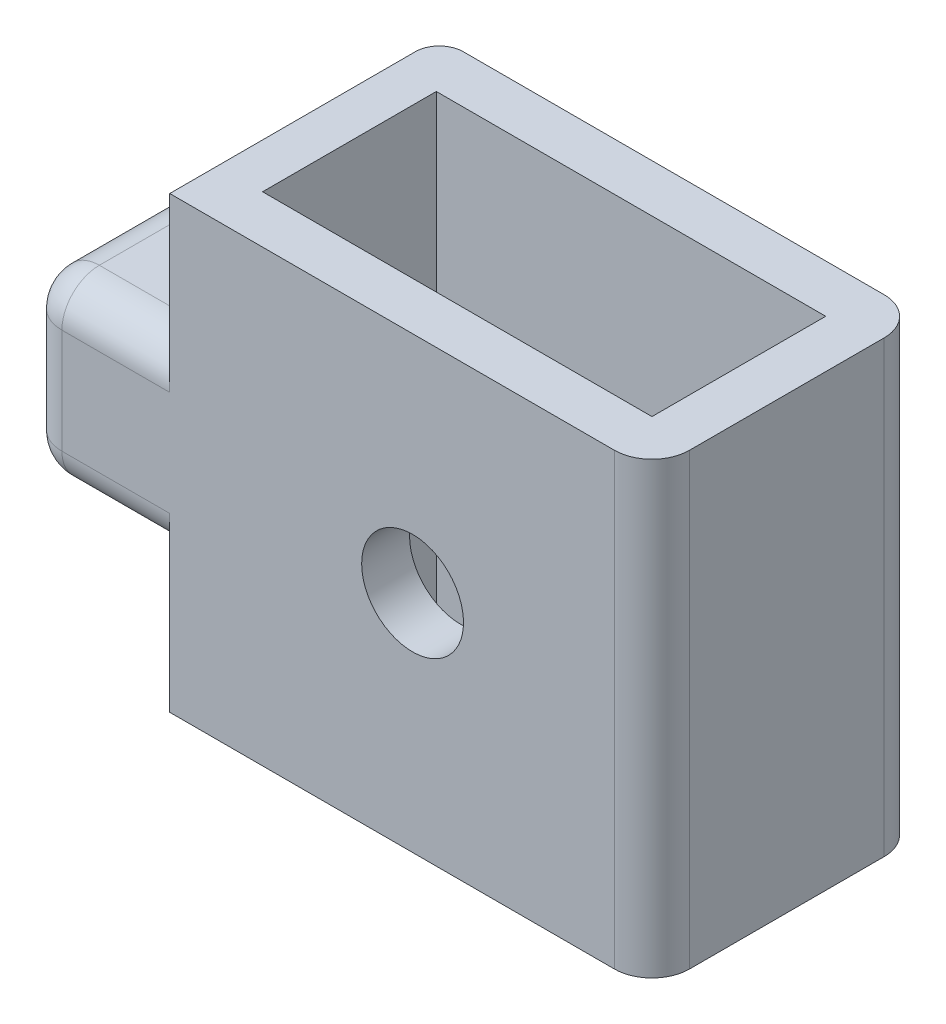
SolidWorks part; units mm, degrees
ref_plane "Спереди" through (0, 0, 0) normal (0, 0, 1) x (1, 0, 0)
ref_plane "Сверху" through (0, 0, 0) normal (0, 1, 0) x (1, 0, 0)
ref_plane "Справа" through (0, 0, 0) normal (1, 0, 0) x (0, 0, -1)
sketch "Эскиз1" plane through (0, 0, 0) normal (0, 1, 0) x (1, 0, 0)
  line L1 (25, 0) -> (394, 0)
  line L2 (0, 25) -> (0, 131.982)
  line L3 (113, 180) -> (394, 180)
  line L4 (419, 25) -> (419, 155)
  line L7 (25, 156.982) -> (91, 156.982)
  line L8 (97, 164) -> (97, 162.982)
  arc A0 (113, 180) -> (97, 164) centre (113, 164) ccw
  arc A1 (91, 156.982) -> (97, 162.982) centre (91, 162.982) ccw
  arc A2 (394, 180) -> (419, 155) centre (394, 155) cw
  arc A3 (394, 0) -> (419, 25) centre (394, 25) ccw
  arc A4 (25, 0) -> (0, 25) centre (25, 25) cw
  arc A5 (0, 131.982) -> (25, 156.982) centre (25, 131.982) cw
  point P2 (0, 0)
  point P18 (0, 0)
  dimension "D1" = 16
  dimension "D2" = 6
  dimension "D3" = 25
extrude "Бобышка-Вытянуть1" add sketch "Эскиз1" along normal blind 300
sketch "Эскиз2" plane through (0, 300, 0) normal (0, 1, 0) x (1, 0, 0)
  line L0 (394, 180) -> (113, 180) construction
  line L1 (127, 148) -> (387, 148)
  line L2 (127, 148) -> (127, 32)
  line L3 (127, 32) -> (387, 32)
  line L4 (387, 148) -> (387, 32)
  line L5 (419, 25) -> (419, 155) construction
  line L6 (25, 0) -> (394, 0) construction
  line L7 (0, 131.982) -> (0, 25) construction
  point P10 (0, 0)
  point P11 (0, 0)
  dimension "D1" = 260
  dimension "D2" = 116
  dimension "D3" = 32
  dimension "D4" = 32
  dimension "D5" = 32
  dimension "D6" = 127
extrude "Вырез-Вытянуть1" cut sketch "Эскиз2" against normal blind 300
sketch "Эскиз3" plane through (0, 300, 0) normal (0, 1, 0) x (1, 0, 0)
  line L0 (127, 148) -> (127, 32) construction
  line L1 (32, 124.982) -> (97, 124.982)
  line L2 (32, 124.982) -> (32, 32)
  line L3 (32, 32) -> (97, 32)
  line L4 (97, 124.982) -> (97, 32)
  line L5 (0, 131.982) -> (0, 25) construction
  line L6 (91, 156.982) -> (25, 156.982) construction
  line L7 (25, 0) -> (394, 0) construction
  point P8 (0, 0)
  dimension "D1" = 65
  dimension "D2" = 92.982
  dimension "D3" = 30
  dimension "D4" = 32
  dimension "D5" = 32
  dimension "D6" = 32
extrude "Вырез-Вытянуть2" cut sketch "Эскиз3" against normal blind 300
sketch "Эскиз5" plane through (0, 0, 0) normal (-1, 0, 0) x (0, 0, 1)
  line L0 (-131.982, 300) -> (-25, 300) construction
  line L1 (-131.982, 0) -> (-25, 0) construction
  line L3 (0, 300) -> (0, 0) construction
  line L4 (-156.982, 300) -> (-156.982, 0) construction
  circle A0 centre (-74.982, 150) radius 29
  dimension "D1" = 58
  dimension "D2" = 150
  dimension "D3" = 150
  dimension "D4" = 74.982
  dimension "D5" = 82
extrude "Вырез-Вытянуть4" cut sketch "Эскиз5" against normal blind 116 contours A0
sketch "Эскиз6" plane through (116, 0, 0) normal (-1, 0, 0) x (0, 0, 1)
  line L0 (-32, 300) -> (-124.982, 300) construction
  line L1 (-156.982, 300) -> (-156.982, 0) construction
  circle A0 centre (-74.982, 150) radius 23
  dimension "D1" = 46
  dimension "D2" = 150
  dimension "D3" = 82
extrude "Вырез-Вытянуть5" cut sketch "Эскиз6" against normal blind 116
sketch "Эскиз7" plane through (0, 0, -180) normal (0, 0, -1) x (-1, 0, 0)
  line L0 (-394, 300) -> (-113, 300) construction
  line L1 (-419, 300) -> (-419, 0) construction
  line L2 (-97, 300) -> (-97, 0) construction
  circle A0 centre (-259.151, 150) radius 34
  dimension "D1" = 68
  dimension "D2" = 150
  dimension "D3" = 159.849
  dimension "D4" = 162.151
extrude "Вырез-Вытянуть6" cut sketch "Эскиз7" against normal blind 216
sketch "Эскиз8" plane through (0, 0, 0) normal (-1, 0, 0) x (0, 0, 1)
  line L6 (-131.982, 300) -> (-131.982, 0) construction
  line L7 (-131.982, 210) -> (-25, 210)
  line L8 (-131.982, 210) -> (-131.982, 200)
  line L9 (-131.982, 200) -> (-25, 200)
  line L10 (-25, 210) -> (-25, 200)
  line L11 (-25, 300) -> (-25, 0) construction
  line L13 (-131.982, 100) -> (-25, 100)
  line L14 (-131.982, 100) -> (-131.982, 90)
  line L15 (-131.982, 90) -> (-25, 90)
  line L16 (-25, 100) -> (-25, 90)
  dimension "D1" = 10
  dimension "D2" = 10
  dimension "D3" = 100
  dimension "D4" = 90
extrude "Бобышка-Вытянуть2" add sketch "Эскиз8" against normal blind 100
sketch "Эскиз9" plane through (0, 300, 0) normal (0, 1, 0) x (1, 0, 0)
  line L1 (97, 162.982) -> (-21.5644, 162.982)
  line L2 (97, 162.982) -> (97, -12.2181)
  line L3 (97, -12.2181) -> (-21.5644, -12.2181)
  line L4 (-21.5644, 162.982) -> (-21.5644, -12.2181)
extrude "Вырез-Вытянуть7" cut sketch "Эскиз9" against normal blind 90
sketch "Эскиз10" plane through (0, 0, 0) normal (0, -1, 0) x (1, 0, 0)
  line L1 (97, -164) -> (-20.9163, -164)
  line L2 (97, -164) -> (97, 12.8719)
  line L3 (97, 12.8719) -> (-20.9163, 12.8719)
  line L4 (-20.9163, -164) -> (-20.9163, 12.8719)
extrude "Вырез-Вытянуть8" cut sketch "Эскиз10" against normal blind 90 contours L2 L1 L4 L3
fillet "Скругление1" radius 25 6 edges at (95.2426, 90, -158.7394) (7.3223, 90, -7.3223) (61, 90, 0) (7.3223, 90, -149.6597) (58, 90, -156.982) (0, 90, -78.491)
fillet "Скругление2" radius 25 6 edges at (95.2426, 210, -158.7394) (58, 210, -156.982) (7.3223, 210, -149.6597) (0, 210, -78.491) (7.3223, 210, -7.3223) (61, 210, 0)
